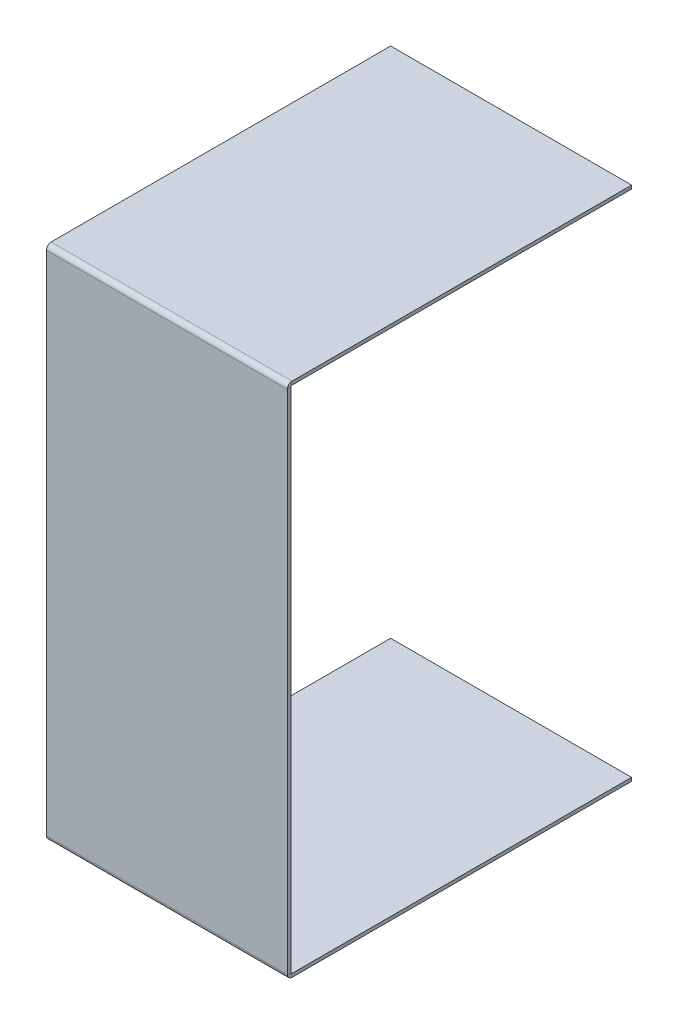
SolidWorks part; units mm, degrees
note: The reader was unsure of these and kept them because the rebuilt part matched: flange length of "Edge-Flange1", "Edge-Flange2".
ref_plane "Front Plane" through (0, 0, 0) normal (0, 0, 1) x (1, 0, 0)
ref_plane "Top Plane" through (0, 0, 0) normal (0, 1, 0) x (1, 0, 0)
ref_plane "Right Plane" through (0, 0, 0) normal (1, 0, 0) x (0, 0, -1)
sketch "Sketch1" plane through (0, 0, 0) normal (0, 0, 1) x (1, 0, 0)
  line L1 (-511.5607, 158.6705) -> (-371.5607, 158.6705)
  line L2 (-511.5607, 158.6705) -> (-511.5607, -141.3295)
  line L3 (-511.5607, -141.3295) -> (-371.5607, -141.3295)
  line L4 (-371.5607, 158.6705) -> (-371.5607, -141.3295)
  dimension "D1" = 300
  dimension "D2" = 140
base flange "Base-Flange1" sketch "Sketch1" thickness 2 reverse thickness direction no parameters "D1"=0.7366
edge flange "Edge-Flange1" sketch "Sketch8" flange angle 90 flange length 200 flange position material inside bend radius 0.7366 thickness 2 relief rectangular parameters "D6"=10
sketch "Sketch8" plane through (0, 158.6705, -2) normal (0, -1, 0) x (-1, 0, 0)
  line L2 (371.5607, 0) -> (371.5607, 198)
  line L3 (371.5607, 198) -> (511.5607, 198)
  line L4 (511.5607, 198) -> (511.5607, 0)
  line L5 (511.5607, 0) -> (371.5607, 0) construction
  line L6 (511.5607, 0) -> (371.5607, 0)
bend "EdgeBend1" bend radius 0.7366 bend angle 90 parameters "D5"=1
edge flange "Edge-Flange2" sketch "Sketch11" flange angle 90 flange length 200 flange position material inside bend radius 0.7366 thickness 2 relief rectangular parameters "D6"=10
sketch "Sketch11" plane through (0, -141.3295, -2) normal (0, -1, 0) x (-1, 0, 0)
  line L0 (511.5607, 0) -> (371.5607, 0) construction
  line L1 (511.5607, 0) -> (371.5607, 0)
  line L2 (371.5607, 0) -> (371.5607, 198)
  line L3 (371.5607, 198) -> (511.5607, 198)
  line L4 (511.5607, 198) -> (511.5607, 0)
bend "EdgeBend2" bend radius 0.7366 bend angle 90 parameters "D5"=2
sketch "Bend-Lines1" [suppressed] plane through (0, 0, 0) normal (0, 1, 0) x (1, 0, 0)
sketch "Bounding-Box1" [suppressed] plane through (0, 0, 0) normal (0, 1, 0) x (1, 0, 0)
sheet metal parameters "Sheet-Metal1" thickness 2 parameters "D1"=0.7366
flat pattern "Flat-Pattern1" [suppressed]
sketch "Bend-Lines2" plane through (0, 0, 0) normal (0, 1, 0) x (1, 0, 0)
sketch3d "Bounding-Box2" [suppressed]
  line L0 (371.5607, 158.6705, 0) -> (371.5607, -141.3295, 0) construction
  line L1 (511.5607, 158.6705, 0) -> (511.5607, -141.3295, 0) construction
  line L2 (371.5607, 158.6705, 0) -> (511.5607, 158.6705, 0) construction
  line L3 (371.5607, -141.3295, 0) -> (511.5607, -141.3295, 0) construction
sheet metal parameters "Sheet-Metal2" thickness 2 parameters "D1"=0.7366
flat pattern "Flat-Pattern1"
sketch "Bend-Lines2" plane through (0, 0, 0) normal (0, 0, 1) x (1, 0, 0)
  line L0 (-371.5607, 157.2978) -> (-511.5607, 157.2978) construction
  line L1 (-371.5607, 157.2978) -> (-511.5607, 157.2978) construction
sketch3d "Bounding-Box2" [suppressed]
  line L0 (-371.5607, 355.9252, 0) -> (-371.5607, -141.3295, 0) construction
  line L1 (-511.5607, 355.9252, 0) -> (-511.5607, -141.3295, 0) construction
  line L2 (-371.5607, 355.9252, 0) -> (-511.5607, 355.9252, 0) construction
  line L3 (-371.5607, -141.3295, 0) -> (-511.5607, -141.3295, 0) construction
bend of the flat pattern "Flatten-<EdgeBend1>1"
sheet metal parameters "Sheet-Metal3" thickness 2 parameters "D1"=0.7366
flat pattern "Flat-Pattern1"
sketch "Bend-Lines2" plane through (0, 0, 0) normal (0, 0, 1) x (1, 0, 0)
  line L0 (-371.5607, 157.2978) -> (-511.5607, 157.2978) construction
  line L1 (-371.5607, 157.2978) -> (-511.5607, 157.2978) construction
  line L2 (-511.5607, -139.9568) -> (-371.5607, -139.9568) construction
  line L3 (-511.5607, -139.9568) -> (-371.5607, -139.9568) construction
sketch3d "Bounding-Box2" [suppressed]
  line L0 (-371.5607, 355.9252, 0) -> (-371.5607, -338.5841, 0) construction
  line L1 (-511.5607, 355.9252, 0) -> (-511.5607, -338.5841, 0) construction
  line L2 (-371.5607, 355.9252, 0) -> (-511.5607, 355.9252, 0) construction
  line L3 (-371.5607, -338.5841, 0) -> (-511.5607, -338.5841, 0) construction
bend of the flat pattern "Flatten-<EdgeBend1>1"
bend of the flat pattern "Flatten-<EdgeBend2>1"
